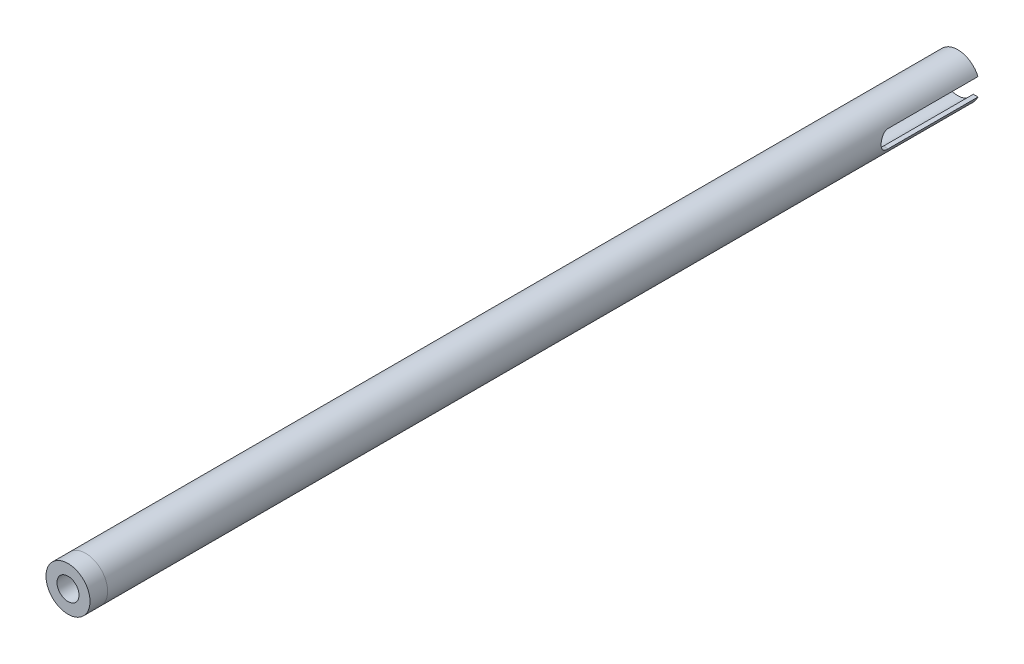
SolidWorks part; units mm, degrees
material "AISI 4130 Steel, annealed at 865C"
ref_plane "Front Plane" through (0, 0, 0) normal (0, 0, 1) x (1, 0, 0)
ref_plane "Top Plane" through (0, 0, 0) normal (0, 1, 0) x (1, 0, 0)
ref_plane "Right Plane" through (0, 0, 0) normal (1, 0, 0) x (0, 0, -1)
sketch "Axis" plane through (0, 0, 0) normal (0, 1, 0) x (1, 0, 0)
  line L0 (0, 0) -> (0, 320.6091) construction
  line L1 (0, 0) -> (0, -34.925) construction
  line L2 (0, 320.6091) -> (-7.9375, 320.6091) construction
  line L3 (0, 349.581) -> (-25.9803, 254.753) construction
  dimension "D1" = 34.925
  dimension "D2" = 7.9375
sketch "Sketch1" plane through (0, 0, 0) normal (0, 0, 1) x (1, 0, 0)
  line L0 (-7.9375, 0) -> (7.9375, 0) construction
  line L1 (-7.2748, 3.175) -> (7.2748, 3.175)
  line L2 (-7.2748, -3.175) -> (7.2748, -3.175)
  circle A0 centre (0, 0) radius 7.9375
  circle A1 centre (0, 0) radius 6.4135
  circle A2 centre (0, 0) radius 3.9688
  dimension "D1" = 15.875
  dimension "D3" = 7.9375
  dimension "D2" = 1.524
  dimension "D4" = 6.35
extrude "Threaded insert 1-1" add sketch "Sketch1" against normal blind 6.35 contours A2 L1 A1 | A1 L1 A0 | A2 L0 A1 L1 | A1 L0 A0 L1 | L0 A1 L2 A0 | L0 A2 L2 A1 | A2 L2 A1 | A1 L2 A0 | L0 A1 L2 A2 | L0 A0 L2 A1 | A0 L0 A1 L1 | A1 L0 A2 L1 region at (4.7887, 1.6543, 0) region at (4.7887, -1.6543, 0) region at (6.9234, 1.6163, 0) region at (6.9234, -1.6163, 0) region at (-4.7887, -1.6543, 0) region at (-4.7887, 1.6543, 0) region at (0, 4.6159, 0) region at (0, -4.6159, 0) region at (0, 6.5666, 0) region at (6.4237, -3.3281, 0) region at (-6.9234, -1.6163, 0) region at (-6.9234, 1.6163, 0)
extrude "Threaded insert 1-2" add sketch "Sketch1<3>" against normal blind 9.525 from surface contours A2 L1 A1 | A2 L0 A1 L1 | L0 A2 L2 A1 | A2 L2 A1 | L0 A1 L2 A2 | A1 L0 A2 L1 region at (4.7887, 1.6543, 0) region at (4.7887, -1.6543, 0) region at (-4.7887, -1.6543, 0) region at (-4.7887, 1.6543, 0) region at (0, 4.6159, 0) region at (0, -4.6159, 0) starting at face at (7.9375, 0, -6.35)
sketch "Sketch1<3>" plane through (0, 0, 0) normal (0, 0, 1) x (1, 0, 0) same geometry as "Sketch1"
extrude "A-arm tube" add sketch "Sketch1<4>" against normal up to vertex (320.6091 mm away) from surface separate body contours A1 L1 A0 | A1 L0 A0 L1 | L0 A1 L2 A0 | A1 L2 A0 | L0 A0 L2 A1 | A0 L0 A1 L1 region at (6.9234, 1.6163, 0) region at (6.9234, -1.6163, 0) region at (0, 6.5666, 0) region at (6.4237, -3.3281, 0) region at (-6.9234, -1.6163, 0) region at (-6.9234, 1.6163, 0) up to point (0, 0, -320.6091) starting at face at (6.4135, 0, -6.35)
sketch "Sketch1<4>" plane through (0, 0, 0) normal (0, 0, 1) x (1, 0, 0) same geometry as "Sketch1"
extrude "Apex slot" cut sketch "Sketch1<5>" along normal blind 35.56 from surface contours A0 L0 A1 L1 | L0 A0 L2 A1 | A1 L0 A0 L1 | L0 A1 L2 A0 region at (6.9234, 1.6163, 0) region at (6.9234, -1.6163, 0) region at (-6.9234, -1.6163, 0) region at (-6.9234, 1.6163, 0) starting at face at (6.4135, 0, -320.6091)
sketch "Sketch1<5>" plane through (0, 0, 0) normal (0, 0, 1) x (1, 0, 0) same geometry as "Sketch1"
fillet "Fillet1" radius 3.175 4 edges at (-6.4237, 3.175, -285.0491) (-6.4237, -3.175, -285.0491) (6.4237, -3.175, -285.0491) (6.4237, 3.175, -285.0491)
equation "\"tube diameter\"= 5 / 8"
equation "\"tube thickness\"= .06"
equation "\"apex thickness\"= .25"
equation "\"tube slot\"= 1.4"
equation "\"D1@Sketch1\"=\"tube diameter\""
equation "\"D2@Sketch1\"=\"tube thickness\""
equation "\"threaded insert hole\"= .3125"
equation "\"D3@Sketch1\"=\"threaded insert hole\""
equation "\"D4@Sketch1\"=\"apex thickness\""
equation "\"D1@Apex slot\" = \"tube slot\""
equation "\"D1@Fillet1\"=\"apex thickness\"/2"
